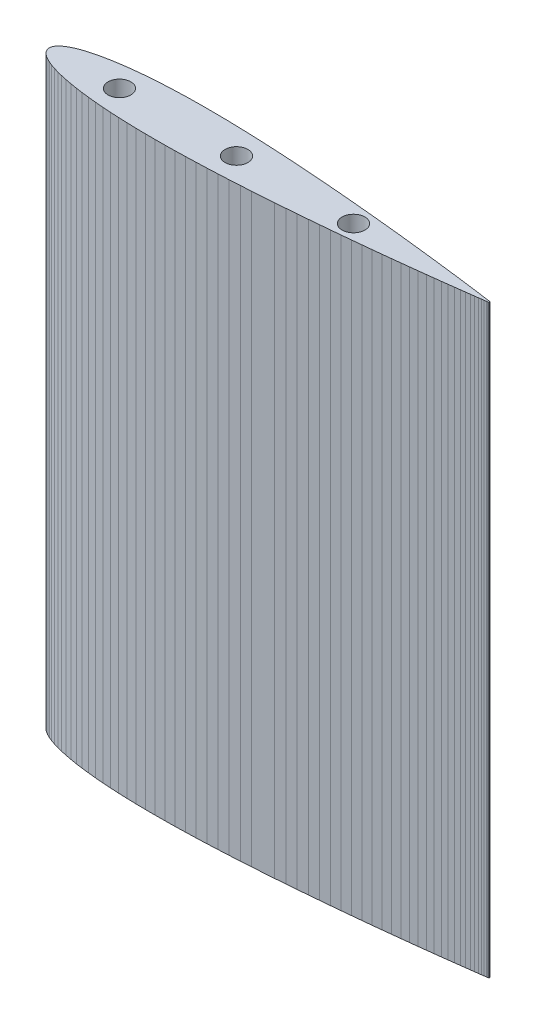
SolidWorks part; units mm, degrees
ref_plane "Front Plane" through (0, 0, 0) normal (0, 0, 1) x (1, 0, 0)
ref_plane "Top Plane" through (0, 0, 0) normal (0, 1, 0) x (1, 0, 0)
ref_plane "Right Plane" through (0, 0, 0) normal (1, 0, 0) x (0, 0, -1)
sketch "Sketch1" plane through (0, 0, 0) normal (0, 1, 0) x (1, 0, 0)
  line L0 (75.2351, 0.0912) -> (75.19, 0.0978)
  line L1 (75.19, 0.0978) -> (75.0621, 0.1204)
  line L2 (75.0621, 0.1204) -> (74.8439, 0.1505)
  line L3 (74.8439, 0.1505) -> (74.5354, 0.1956)
  line L4 (74.5354, 0.1956) -> (74.1442, 0.2483)
  line L5 (74.1442, 0.2483) -> (73.6627, 0.316)
  line L6 (73.6627, 0.316) -> (73.106, 0.3912)
  line L7 (73.106, 0.3912) -> (72.4589, 0.474)
  line L8 (72.4589, 0.474) -> (71.7292, 0.5718)
  line L9 (71.7292, 0.5718) -> (70.9241, 0.6771)
  line L10 (70.9241, 0.6771) -> (70.0439, 0.79)
  line L11 (70.0439, 0.79) -> (69.0809, 0.9179)
  line L12 (69.0809, 0.9179) -> (68.0502, 1.0458)
  line L13 (68.0502, 1.0458) -> (66.9442, 1.1812)
  line L14 (66.9442, 1.1812) -> (65.7781, 1.3241)
  line L15 (65.7781, 1.3241) -> (64.5367, 1.4746)
  line L16 (64.5367, 1.4746) -> (63.2351, 1.6251)
  line L17 (63.2351, 1.6251) -> (61.8734, 1.7831)
  line L18 (61.8734, 1.7831) -> (60.4589, 1.9411)
  line L19 (60.4589, 1.9411) -> (58.9843, 2.1066)
  line L20 (58.9843, 2.1066) -> (57.4646, 2.2721)
  line L21 (57.4646, 2.2721) -> (55.8997, 2.4301)
  line L22 (55.8997, 2.4301) -> (54.2897, 2.5956)
  line L23 (54.2897, 2.5956) -> (52.642, 2.7611)
  line L24 (52.642, 2.7611) -> (50.9567, 2.9191)
  line L25 (50.9567, 2.9191) -> (49.2414, 3.0771)
  line L26 (49.2414, 3.0771) -> (47.5034, 3.2351)
  line L27 (47.5034, 3.2351) -> (45.7354, 3.3856)
  line L28 (45.7354, 3.3856) -> (43.9524, 3.5285)
  line L29 (43.9524, 3.5285) -> (42.1542, 3.6715)
  line L30 (42.1542, 3.6715) -> (40.3411, 3.7994)
  line L31 (40.3411, 3.7994) -> (38.5279, 3.9273)
  line L32 (38.5279, 3.9273) -> (36.7072, 4.0401)
  line L33 (36.7072, 4.0401) -> (34.894, 4.1455)
  line L34 (34.894, 4.1455) -> (33.0809, 4.2357)
  line L35 (33.0809, 4.2357) -> (31.2828, 4.3185)
  line L36 (31.2828, 4.3185) -> (29.4997, 4.3862)
  line L37 (29.4997, 4.3862) -> (27.7317, 4.4389)
  line L38 (27.7317, 4.4389) -> (25.9937, 4.484)
  line L39 (25.9937, 4.484) -> (24.2784, 4.5066)
  line L40 (24.2784, 4.5066) -> (22.5931, 4.5141)
  line L41 (22.5931, 4.5141) -> (20.9455, 4.5066)
  line L42 (20.9455, 4.5066) -> (19.3354, 4.484)
  line L43 (19.3354, 4.484) -> (17.7705, 4.4389)
  line L44 (17.7705, 4.4389) -> (16.2508, 4.3787)
  line L45 (16.2508, 4.3787) -> (14.7762, 4.3034)
  line L46 (14.7762, 4.3034) -> (13.3618, 4.2056)
  line L47 (13.3618, 4.2056) -> (12, 4.0928)
  line L48 (12, 4.0928) -> (10.6984, 3.9574)
  line L49 (10.6984, 3.9574) -> (9.4571, 3.8144)
  line L50 (9.4571, 3.8144) -> (8.2909, 3.6489)
  line L51 (8.2909, 3.6489) -> (7.185, 3.4608)
  line L52 (7.185, 3.4608) -> (6.1542, 3.2652)
  line L53 (6.1542, 3.2652) -> (5.1912, 3.0545)
  line L54 (5.1912, 3.0545) -> (4.311, 2.8288)
  line L55 (4.311, 2.8288) -> (3.506, 2.5956)
  line L56 (3.506, 2.5956) -> (2.7762, 2.3473)
  line L57 (2.7762, 2.3473) -> (2.1292, 2.084)
  line L58 (2.1292, 2.084) -> (1.5724, 1.8132)
  line L59 (1.5724, 1.8132) -> (1.0909, 1.5273)
  line L60 (1.0909, 1.5273) -> (0.6997, 1.2414)
  line L61 (0.6997, 1.2414) -> (0.3912, 0.9404)
  line L62 (0.3912, 0.9404) -> (0.173, 0.632)
  line L63 (0.173, 0.632) -> (0.0451, 0.3235)
  line L64 (0.0451, 0.3235) -> (0, 0)
  line L65 (0, 0) -> (0.0451, -0.3235)
  line L66 (0.0451, -0.3235) -> (0.173, -0.632)
  line L67 (0.173, -0.632) -> (0.3912, -0.9404)
  line L68 (0.3912, -0.9404) -> (0.6997, -1.2414)
  line L69 (0.6997, -1.2414) -> (1.0909, -1.5273)
  line L70 (1.0909, -1.5273) -> (1.5724, -1.8132)
  line L71 (1.5724, -1.8132) -> (2.1292, -2.084)
  line L72 (2.1292, -2.084) -> (2.7762, -2.3473)
  line L73 (2.7762, -2.3473) -> (3.506, -2.5956)
  line L74 (3.506, -2.5956) -> (4.311, -2.8288)
  line L75 (4.311, -2.8288) -> (5.1912, -3.0545)
  line L76 (5.1912, -3.0545) -> (6.1542, -3.2652)
  line L77 (6.1542, -3.2652) -> (7.185, -3.4608)
  line L78 (7.185, -3.4608) -> (8.2909, -3.6489)
  line L79 (8.2909, -3.6489) -> (9.4571, -3.8144)
  line L80 (9.4571, -3.8144) -> (10.6984, -3.9574)
  line L81 (10.6984, -3.9574) -> (12, -4.0928)
  line L82 (12, -4.0928) -> (13.3618, -4.2056)
  line L83 (13.3618, -4.2056) -> (14.7762, -4.3034)
  line L84 (14.7762, -4.3034) -> (16.2508, -4.3787)
  line L85 (16.2508, -4.3787) -> (17.7705, -4.4389)
  line L86 (17.7705, -4.4389) -> (19.3354, -4.484)
  line L87 (19.3354, -4.484) -> (20.9455, -4.5066)
  line L88 (20.9455, -4.5066) -> (22.5931, -4.5141)
  line L89 (22.5931, -4.5141) -> (24.2784, -4.5066)
  line L90 (24.2784, -4.5066) -> (25.9937, -4.484)
  line L91 (25.9937, -4.484) -> (27.7317, -4.4389)
  line L92 (27.7317, -4.4389) -> (29.4997, -4.3862)
  line L93 (29.4997, -4.3862) -> (31.2828, -4.3185)
  line L94 (31.2828, -4.3185) -> (33.0809, -4.2357)
  line L95 (33.0809, -4.2357) -> (34.894, -4.1455)
  line L96 (34.894, -4.1455) -> (36.7072, -4.0401)
  line L97 (36.7072, -4.0401) -> (38.5279, -3.9273)
  line L98 (38.5279, -3.9273) -> (40.3411, -3.7994)
  line L99 (40.3411, -3.7994) -> (42.1542, -3.6715)
  line L100 (42.1542, -3.6715) -> (43.9524, -3.5285)
  line L101 (43.9524, -3.5285) -> (45.7354, -3.3856)
  line L102 (45.7354, -3.3856) -> (47.5034, -3.2351)
  line L103 (47.5034, -3.2351) -> (49.2414, -3.0771)
  line L104 (49.2414, -3.0771) -> (50.9567, -2.9191)
  line L105 (50.9567, -2.9191) -> (52.642, -2.7611)
  line L106 (52.642, -2.7611) -> (54.2897, -2.5956)
  line L107 (54.2897, -2.5956) -> (55.8997, -2.4301)
  line L108 (55.8997, -2.4301) -> (57.4646, -2.2721)
  line L109 (57.4646, -2.2721) -> (58.9843, -2.1066)
  line L110 (58.9843, -2.1066) -> (60.4589, -1.9411)
  line L111 (60.4589, -1.9411) -> (61.8734, -1.7831)
  line L112 (61.8734, -1.7831) -> (63.2351, -1.6251)
  line L113 (63.2351, -1.6251) -> (64.5367, -1.4746)
  line L114 (64.5367, -1.4746) -> (65.7781, -1.3241)
  line L115 (65.7781, -1.3241) -> (66.9442, -1.1812)
  line L116 (66.9442, -1.1812) -> (68.0502, -1.0458)
  line L117 (68.0502, -1.0458) -> (69.0809, -0.9179)
  line L118 (69.0809, -0.9179) -> (70.0439, -0.79)
  line L119 (70.0439, -0.79) -> (70.9241, -0.6771)
  line L120 (70.9241, -0.6771) -> (71.7292, -0.5718)
  line L121 (71.7292, -0.5718) -> (72.4589, -0.474)
  line L122 (72.4589, -0.474) -> (73.106, -0.3912)
  line L123 (73.106, -0.3912) -> (73.6627, -0.316)
  line L124 (73.6627, -0.316) -> (74.1442, -0.2483)
  line L125 (74.1442, -0.2483) -> (74.5354, -0.1956)
  line L126 (74.5354, -0.1956) -> (74.8439, -0.1505)
  line L127 (74.8439, -0.1505) -> (75.0621, -0.1204)
  line L128 (75.0621, -0.1204) -> (75.19, -0.0978)
  line L129 (75.19, -0.0978) -> (75.2351, -0.0887)
  line L130 (0, 0) -> (75.2351, 0) construction
  line L131 (75.2351, 0.0912) -> (75.2351, -0.0887)
extrude "Boss-Extrude1" add sketch "Sketch1" along normal mid plane 100
sketch "Sketch2" plane through (0, 50, 0) normal (0, 1, 0) x (1, 0, 0)
  line L0 (0, 0) -> (75.2351, 0.0012) construction
  line L1 (75.2351, -0.0887) -> (75.2351, 0.0912) construction
  circle A0 centre (12, 0.0002) radius 1.95
  circle A1 centre (32, 0.0005) radius 1.95
  circle A2 centre (52, 0.0009) radius 1.95
  dimension "D1" = 3.9
  dimension "D2" = 3.9
  dimension "D3" = 3.9
  dimension "D4" = 12
  dimension "D5" = 20
  dimension "D6" = 20
extrude "Cut-Extrude1" cut sketch "Sketch2" against normal blind 15
mirror "Mirror1" about plane through (0, 0, 0) normal (0, 1, 0) of "Cut-Extrude1"
